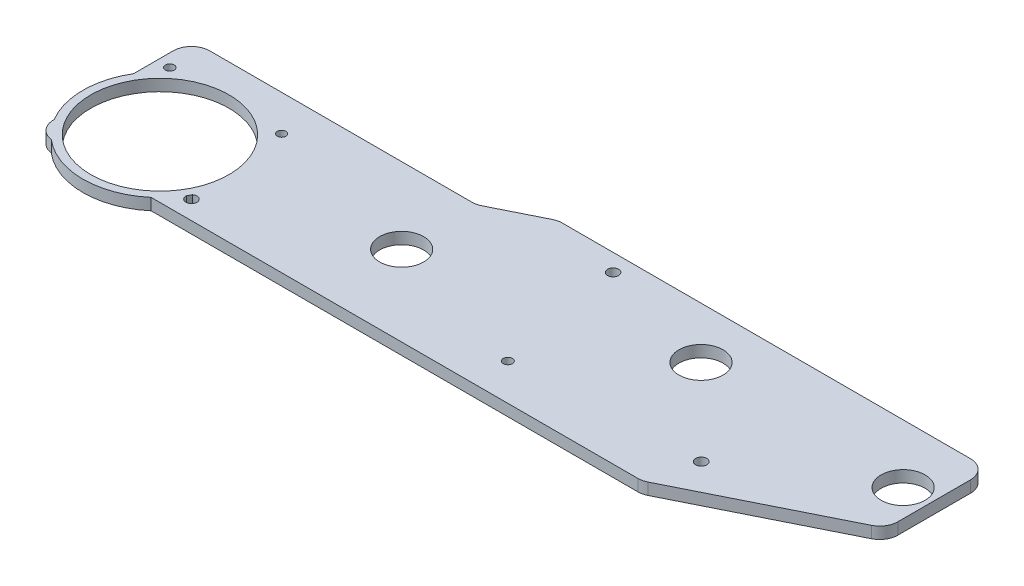
SolidWorks part; units mm, degrees
ref_plane "Front" through (0, 0, 0) normal (0, 0, 1) x (1, 0, 0)
ref_plane "Top" through (0, 0, 0) normal (0, 1, 0) x (1, 0, 0)
ref_plane "Right" through (0, 0, 0) normal (1, 0, 0) x (0, 0, -1)
sketch "Sketch1" plane through (0, 0, 0) normal (0, 1, 0) x (1, 0, 0)
  line L1 (0, 0) -> (210, 0)
  line L2 (0, 0) -> (0, -50)
  line L3 (0, -50) -> (210, -50)
  line L4 (210, 0) -> (210, -50)
  circle A7 centre (3.4895, -16.7877) radius 1.2117
  circle A8 centre (34.3726, -17.194) radius 1.1656
  circle A9 centre (37.5207, -44.9212) radius 1.5
  circle A10 centre (118.879, -40.0177) radius 1.25
  circle A11 centre (112.3021, -4.7393) radius 1.5
  circle A12 centre (168.9752, -37.4032) radius 1.5173
  dimension "D1" = 210
  dimension "D2" = 50
extrude "Boss-Extrude1" add sketch "Sketch1" along normal blind 3.175
sketch "Sketch2" plane through (0, 3.175, 0) normal (0, 1, 0) x (1, 0, 0)
  line L0 (210, 0) -> (0, 0) construction
  line L1 (0, 0) -> (0, -50) construction
  circle A0 centre (10, -26) radius 2
  circle A1 centre (10, -42) radius 2
  circle A2 centre (26, -26) radius 2
  circle A3 centre (26, -42) radius 2
  dimension "D1" = 16
  dimension "D2" = 16
  dimension "D3" = 16
  dimension "D4" = 26
  dimension "D5" = 10
  dimension "D6" = 10
  dimension "D7" = 26
  dimension "D8" = 16
extrude "Cut-Extrude1" cut sketch "Sketch2" against normal blind 10
sketch "Sketch3" plane through (0, 3.175, 0) normal (0, 1, 0) x (1, 0, 0)
  line L0 (210, 0) -> (0, 0) construction
  line L1 (210, 0) -> (0, 0) construction
  circle A0 centre (78.0103, -28.1) radius 6
  circle A1 centre (145.5313, -14) radius 6
  circle A2 centre (18, -34) radius 0.587
  circle A3 centre (26, -26) radius 2 construction
  circle A4 centre (202.6463, -16) radius 6
  dimension "D1" = 28.1
  dimension "D3" = 16
  dimension "D4" = 14
  dimension "D7" = 125.222
  dimension "D2" = 60.2996
  dimension "D5" = 8
  dimension "D6" = 8
  dimension "D8" = 57.15
extrude "Cut-Extrude2" cut sketch "Sketch3" against normal blind 57.15
sketch "Sketch4" [suppressed] plane through (0, 3.175, 0) normal (0, 1, 0) x (1, 0, 0)
  line L0 (3.4895, -16.7877) -> (18, -34)
  line L1 (3.4895, -20.6627) -> (5.9498, -23.5811)
  line L2 (18, -34) -> (34.3726, -17.194)
  line L3 (34.3726, -17.194) -> (75.8499, -28.1)
  line L4 (75.8499, -28.1) -> (37.5207, -44.9212)
  line L5 (7.3432, -17.194) -> (9.8664, -20.303)
  circle A0 centre (18, -34) radius 15.9299
  circle A1 centre (3.4895, -16.7877) radius 3.8751
  circle A2 centre (34.3726, -17.194) radius 3.7227
  circle A3 centre (37.5207, -44.9212) radius 3.8676
  circle A4 centre (75.8499, -28.1) radius 12.797
  circle A5 centre (112.3021, -4.7393) radius 5.1588
  circle A6 centre (118.879, -40.0177) radius 4.9035
  circle A7 centre (140.772, -16) radius 12.6375
  circle A8 centre (168.9752, -37.4032) radius 4.2066
  circle A9 centre (197.922, -16) radius 12.8
sketch "Sketch5" [suppressed] plane through (0, 3.175, 0) normal (0, 1, 0) x (1, 0, 0)
  line L0 (210, 0) -> (0, 0) construction
  line L2 (-0.6266, -16.7877) -> (37.5207, -16.7877)
  line L3 (-0.6266, -16.7877) -> (-0.6266, -44.9212)
  line L4 (-0.6266, -44.9212) -> (37.5207, -44.9212)
  line L5 (37.5207, -16.7877) -> (37.5207, -44.9212)
  line L6 (75.8499, -15.182) -> (37.5207, -15.182)
  line L7 (75.8499, -15.182) -> (75.8499, -44.9212)
  line L8 (75.8499, -44.9212) -> (37.5207, -44.9212)
  line L9 (37.5207, -15.182) -> (37.5207, -44.9212)
  line L10 (112.3021, -4.7393) -> (75.8499, -4.7393)
  line L11 (112.3021, -4.7393) -> (112.3021, -44.9212)
  line L12 (112.3021, -44.9212) -> (75.8499, -44.9212)
  line L13 (75.8499, -4.7393) -> (75.8499, -44.9212)
  line L14 (112.3021, -4.7393) -> (102.3945, -4.7393)
  line L16 (112.3021, -4.7393) -> (112.3021, 0)
  line L17 (112.3021, 0) -> (102.3945, 0)
  line L18 (102.3945, -4.7393) -> (102.3945, 0)
  line L19 (210, -50) -> (210, 0) construction
  line L20 (112.3021, -4.7393) -> (123.1553, -4.7393)
  line L21 (112.3021, -4.7393) -> (112.3021, 0)
  line L22 (112.3021, 0) -> (123.1553, 0)
  line L23 (123.1553, -4.7393) -> (123.1553, 0)
  line L24 (112.3021, -4.7393) -> (140.772, -4.7393)
  line L25 (112.3021, -4.7393) -> (112.3021, -40.0177)
  line L26 (112.3021, -40.0177) -> (140.772, -40.0177)
  line L27 (140.772, -4.7393) -> (140.772, -40.0177)
  line L28 (140.772, -16) -> (168.9752, -16)
  line L29 (140.772, -16) -> (140.772, -40.0177)
  line L30 (140.772, -40.0177) -> (168.9752, -40.0177)
  line L31 (168.9752, -16) -> (168.9752, -40.0177)
  line L32 (168.9752, -4.7393) -> (210, -4.7393)
  line L33 (168.9752, -4.7393) -> (168.9752, -40.0177)
  line L34 (168.9752, -40.0177) -> (210, -40.0177)
  line L35 (210, -4.7393) -> (210, -40.0177)
  line L36 (0, -50) -> (210, -50) construction
  line L37 (160.7629, -40.0177) -> (177.2091, -40.0177)
  line L38 (160.7629, -40.0177) -> (160.7629, -44.9212)
  line L39 (160.7629, -44.9212) -> (177.2091, -44.9212)
  line L40 (177.2091, -40.0177) -> (177.2091, -44.9212)
  line L41 (112.3021, -40.0177) -> (126.3591, -40.0177)
  line L42 (112.3021, -40.0177) -> (112.3021, -47.7828)
  line L43 (112.3021, -47.7828) -> (126.3591, -47.7828)
  line L44 (126.3591, -40.0177) -> (126.3591, -47.7828)
  line L45 (30.5963, -44.9212) -> (44.6115, -44.9212)
  line L46 (30.5963, -44.9212) -> (30.5963, -50)
  line L47 (30.5963, -50) -> (44.6115, -50)
  line L48 (44.6115, -44.9212) -> (44.6115, -50)
  line L50 (-0.6266, -44.9212) -> (30.5963, -44.9212)
  line L51 (-0.6266, -44.9212) -> (-0.6266, -50)
  line L52 (-0.6266, -50) -> (30.5963, -50)
  line L53 (30.5963, -44.9212) -> (30.5963, -50)
  circle A0 centre (3.4895, -16.7877) radius 4.1161
  circle A1 centre (34.3726, -17.194) radius 3.8132
  circle A2 centre (75.8499, -28.1) radius 12.918
  circle A3 centre (112.3021, -4.7393) radius 5.2663
  circle A4 centre (140.772, -16) radius 13.0245
  circle A5 centre (197.922, -16) radius 12.3805
  circle A6 centre (168.9752, -37.4032) radius 4.7643
  circle A7 centre (118.879, -40.0177) radius 5.279
  circle A8 centre (37.5207, -44.9212) radius 4.2049
  line M12 (0, 0) -> (0, -50)
  line M13 (0, -50) -> (210, -50)
  line M14 (210, -50) -> (210, 0)
  line M15 (210, 0) -> (0, 0)
extrude "Cut-Extrude5" [suppressed] cut sketch "Sketch5" against normal blind 11.52 contours A5 L32 L23 L24 A4 L28 L33 M14 M15 | A1 L6 L13 L10 L18 A0 L2 M15 M12 | L8 L48 L34 L40 L39 L38 L30 L26 L44 L43 L42 L12 M13 M14
fillet "Fillet1" [suppressed] radius 5
sketch "Sketch10" plane through (0, 3.175, 0) normal (0, 1, 0) x (1, 0, 0)
  line L0 (210, -27.8594) -> (165.5029, -50)
  line L1 (210, -50) -> (210, 0) construction
  line L2 (0, -50) -> (210, -50) construction
  line L3 (165.5029, -50) -> (210, -50)
  line L4 (210, -50) -> (210, -27.8594)
  line L5 (92.5326, 0) -> (77.6548, -7.4028)
  line L6 (210, 0) -> (0, 0) construction
  line L7 (77.6548, -7.4028) -> (0, -7.4028)
  line L8 (0, 0) -> (0, -50) construction
  line L9 (0, -7.4028) -> (0, 0)
  line L10 (0, 0) -> (92.5326, 0)
extrude "Cut-Extrude7" cut sketch "Sketch10" against normal blind 10
fillet "Fillet3" radius 5 7 edges at (0, 1.5875, 50) (0, 1.5875, 7.4028) (77.6548, 1.5875, 7.4028) (92.5326, 1.5875, 0) (210, 1.5875, 0) (210, 1.5875, 27.8594) (165.5029, 1.5875, 50)
sketch "Sketch11" plane through (0, 3.175, 0) normal (0, 1, 0) x (1, 0, 0)
  circle A0 centre (18, -34) radius 18.5
  circle A1 centre (10, -26) radius 2
  circle A2 centre (10, -42) radius 2
  circle A3 centre (26, -26) radius 2
  circle A4 centre (26, -42) radius 2
extrude "Boss-Extrude4" add sketch "Sketch11" against normal blind 3.175
sketch "Sketch12" plane through (0, 3.175, 0) normal (0, 1, 0) x (1, 0, 0)
  circle A0 centre (18, -34) radius 21
  circle A1 centre (10, -26) radius 2 construction
  circle A2 centre (10, -42) radius 2 construction
  dimension "D1" = 8
  dimension "D2" = 8
extrude "Boss-Extrude5" add sketch "Sketch12" against normal blind 3.175
sketch "Sketch13" plane through (0, 3.175, 0) normal (0, 1, 0) x (1, 0, 0)
  circle A0 centre (18, -34) radius 18.85
extrude "Cut-Extrude8" cut sketch "Sketch13" against normal blind 3.175
